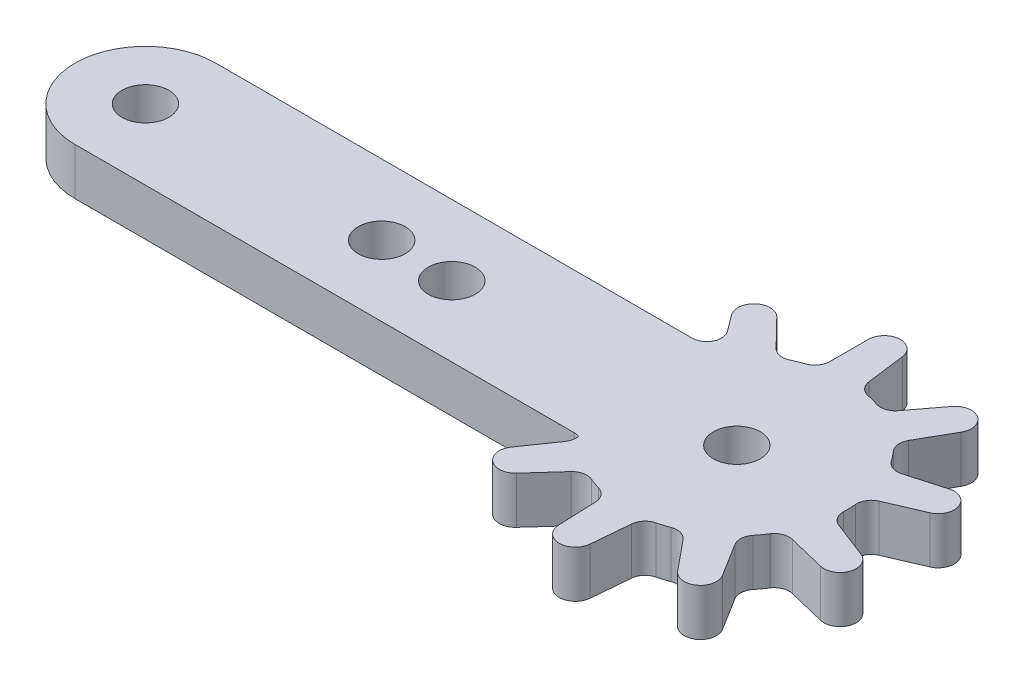
SolidWorks part; units mm, degrees
ref_plane "Alzado" through (0, 0, 0) normal (0, 0, 1) x (1, 0, 0)
ref_plane "Planta" through (0, 0, 0) normal (0, 1, 0) x (1, 0, 0)
ref_plane "Vista lateral" through (0, 0, 0) normal (1, 0, 0) x (0, 0, -1)
sketch "Croquis1" plane through (0, 0, 0) normal (0, 1, 0) x (1, 0, 0)
  line L1 (-20, 0) -> (20, 0)
  line L3 (-20, -9.525) -> (20, -9.525)
  arc A0 (-20, 0) -> (-20, -9.525) centre (-20, -4.7625) ccw
  arc A1 (20, -9.525) -> (20, 0) centre (20, -4.7625) ccw
  circle A2 centre (-20, -4.7625) radius 1.5875
  circle A3 centre (20, -4.7625) radius 1.5875
  dimension "D3" = 4.7625
  dimension "D5" = 3.175
  dimension "D6" = 3.175
  dimension "D1" = 40
  dimension "D2" = 9.525
  dimension "D4" = 40
extrude "Saliente-Extruir1" add sketch "Croquis1" along normal blind 3.175
sketch "Croquis2" plane through (0, 3.175, 0) normal (0, 1, 0) x (1, 0, 0)
  line L0 (20, -1004.7625) -> (20, 48995.2375) construction
  circle A0 centre (20, -4.7625) radius 7.5
  circle A1 centre (20, 14.7375) radius 9 construction
  circle A2 centre (20, -4.7625) radius 1.5875
  dimension "D1" = 15
  dimension "D2" = 18
  dimension "D3" = 19.5
extrude "Saliente-Extruir2" add sketch "Croquis2" against normal blind 3.175
sketch "Croquis8" plane through (0, 3.175, 0) normal (0, 1, 0) x (1, 0, 0)
  line L0 (20, -4.7625) -> (-29071.9665, 40660.4252) construction
  line L1 (20, -4.7625) -> (-22676.5039, 22236.8096) construction
  line L2 (20, -4.7625) -> (-23649.2675, 19451.2229) construction
  line L3 (20, -4.7625) -> (-25417.0581, 43041.2138) construction
  line L4 (11.6078, 3.4615) -> (14.2062, 0)
  line L6 (13.1634, 4.7938) -> (16.1844, 1.6944)
  arc A1 (16.1844, 1.6944) -> (14.2062, 0) centre (20, -4.7625) ccw
  arc A2 (13.1634, 4.7938) -> (11.6078, 3.4615) centre (20, -4.7625) ccw
  arc A3 (14.2062, -9.525) -> (14.2062, 0) centre (20, -4.7625) ccw construction
  dimension "D1" = 23.5
  dimension "D2" = 5
  dimension "D3" = 10
  dimension "D4" = 5
extrude "Saliente-Extruir3" add sketch "Croquis8" against normal blind 3.175
sketch "Croquis9" plane through (0, 3.175, 0) normal (0, 1, 0) x (1, 0, 0)
  line L0 (16.1844, 1.6944) -> (13.1634, 4.7938) construction
  line L1 (11.6078, 3.4615) -> (14.2062, 0) construction
  line L2 (11.6078, 3.4615) -> (12.194, 2.6806)
  line L3 (13.8449, 4.0946) -> (13.1634, 4.7938)
  arc A0 (13.8449, 4.0946) -> (12.194, 2.6806) centre (13.065, 3.3344) ccw
  arc A1 (13.1634, 4.7938) -> (11.6078, 3.4615) centre (20, -4.7625) ccw construction
  arc A2 (13.1634, 4.7938) -> (11.6078, 3.4615) centre (20, -4.7625) ccw
  line M6 (16.1844, 1.6944) -> (13.1634, 4.7938)
  arc M7 (13.1634, 4.7938) -> (11.6078, 3.4615) centre (20, -4.7625) ccw
  line M8 (11.6078, 3.4615) -> (14.2062, 0)
extrude "Cortar-Extruir4" cut sketch "Croquis9" against normal blind 10 contours A0 M7 M8 | A0 M6 M7 region at (11.8961, 3.175, -3.4495) region at (13.1309, 3.175, -4.5071)
pattern_circular "MatrizC1" count 8 every 37 about axis through (20, 0, 4.7625) along (0, 1, 0) of "Saliente-Extruir3", "Cortar-Extruir4" reverse direction yes
fillet "Redondeo1" radius 1 17 edges at (14.2062, 1.5875, 9.525) (14.3898, 1.5875, 9.74) (16.4305, 1.5875, 11.3586) (18.515, 1.5875, 12.114) (21.1189, 1.5875, 12.1786) (23.2383, 1.5875, 11.5274) (25.3567, 1.5875, 10.0118) (26.6574, 1.5875, 8.2163) (27.4372, 1.5875, 5.7311) (27.3954, 1.5875, 3.5143) (26.5225, 1.5875, 1.0602) (20.8386, 1.5875, -2.6905) (22.981, 1.5875, -2.1196) (14.2062, 1.5875, 0) (18.239, 1.5875, -2.5278) (16.1844, 1.5875, -1.6944) (25.1551, 1.5875, -0.685)
sketch "Esquisse1" plane through (0, 3.175, 0) normal (0, 1, 0) x (1, 0, 0)
  circle A0 centre (0.72, -4.7625) radius 1.59
  circle A1 centre (-4.02, -4.7625) radius 1.59
  dimension "D3" = 3.18
  dimension "D1" = 19.28
  dimension "D2" = 24.02
extrude "Enlèv. mat.-Extru.1" cut sketch "Esquisse1" against normal through all
